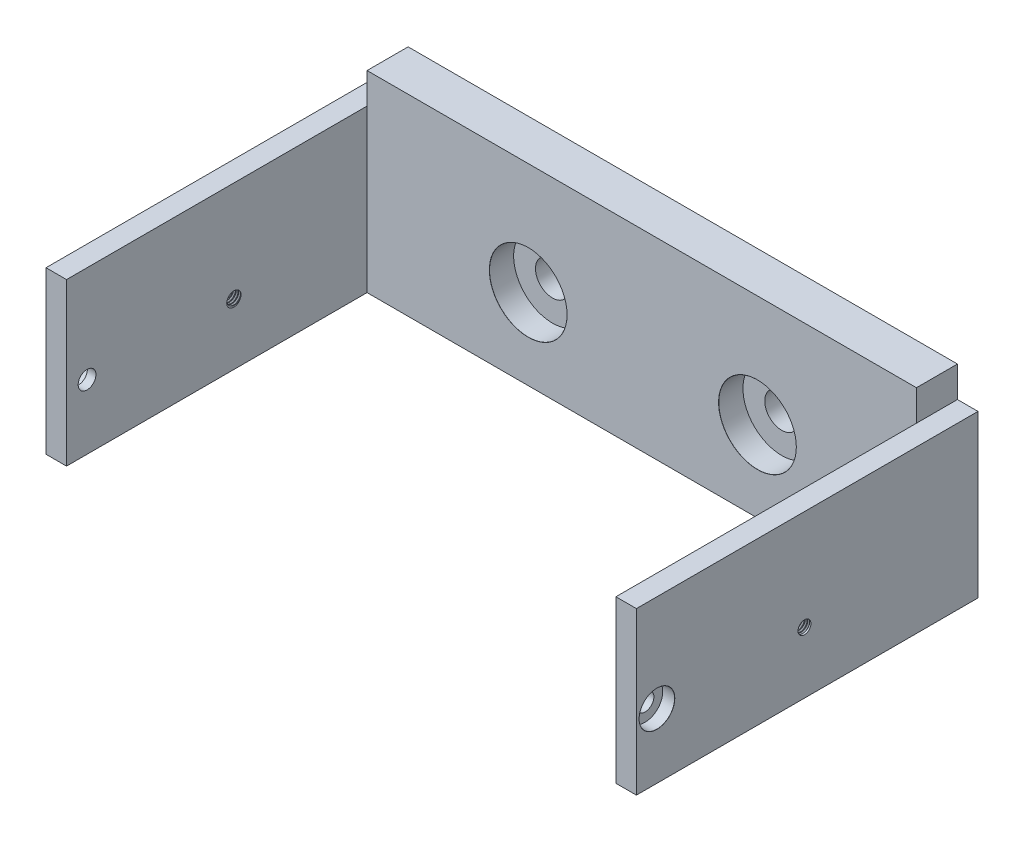
SolidWorks part; units mm, degrees
material "Liga 1060"
ref_plane "Plano frontal" through (0, 0, 0) normal (0, 0, 1) x (1, 0, 0)
ref_plane "Plano superior" through (0, 0, 0) normal (0, 1, 0) x (1, 0, 0)
ref_plane "Plano direito" through (0, 0, 0) normal (1, 0, 0) x (0, 0, -1)
sketch "Esboço1" plane through (0, 0, 0) normal (0, 0, 1) x (1, 0, 0)
  line L1 (85, -29.76) -> (-85, -29.76)
  line L2 (85, -29.76) -> (85, 29.76)
  line L3 (85, 29.76) -> (-85, 29.76)
  line L4 (-85, -29.76) -> (-85, 29.76)
  line L5 (85, -29.76) -> (-85, 29.76) construction
  line L6 (85, 29.76) -> (-85, -29.76) construction
  point P0 (0, 0)
  dimension "D1" = 170
  dimension "D2" = 59.52
extrude "Ressalto-extrusão1" add sketch "Esboço1" along normal blind 12.7
sketch "Esboço2" plane through (0, 0, 0) normal (0, 0, 1) x (1, 0, 0)
  line L0 (-85, 20.24) -> (-85, -29.76)
  line L1 (-85, 20.24) -> (-91.35, 20.24)
  line L2 (-85, -29.76) -> (-91.35, -29.76)
  line L3 (-91.35, 20.24) -> (-91.35, -29.76)
  line L4 (85, 20.24) -> (85, -29.76)
  line L5 (85, 20.24) -> (91.35, 20.24)
  line L6 (85, -29.76) -> (91.35, -29.76)
  line L7 (91.35, 20.24) -> (91.35, -29.76)
  dimension "D1" = 50
  dimension "D2" = 50
  dimension "D3" = 6.35
  dimension "D4" = 6.35
extrude "Ressalto-extrusão3" add sketch "Esboço2" along normal blind 105.7
sketch "Esboço3" plane through (91.35, 0, 0) normal (1, 0, 0) x (0, 0, -1)
  line L2 (-99.35, -29.76) -> (-99.35, 20.24) construction
  line L3 (-105.7, 20.24) -> (0, 20.24) construction
  line L4 (-105.7, -29.76) -> (0, -29.76) construction
  line L5 (-105.7, -29.76) -> (-105.7, 20.24) construction
  circle A0 centre (-99.35, -9.76) radius 2.5
  dimension "D2" = 5
  dimension "D1" = 6.35
  dimension "D3" = 20
extrude "Corte-extrusão2" cut sketch "Esboço3" against normal up to surface (6.35 mm away) up to face at (85, -4.76, 59.2)
mirror "Espelhar1" about plane through (0, 0, 0) normal (1, 0, 0) of "Corte-extrusão2"
hole_wizard "Rebaixo para parafuso com cabeça panela de M51" positions "Esboço7" profile "Esboço8" counterbore size "M5" standard "ISO" end condition through all
sketch "Esboço7" plane through (-91.35, 0, 0) normal (-1, 0, 0) x (0, 0, 1)
  point P0 (99.35, -9.76)
sketch "Esboço8" plane through (-91.35, -9.76, 99.35) normal (0, 1, 0) x (0, 0, 1)
  line L0 (0, 0) -> (0, 182.7)
  line L1 (0, 182.7) -> (2.75, 182.7)
  line L3 (2.75, 182.7) -> (2.75, 3.7)
  line L4 (5.5, 3.7) -> (2.75, 3.7)
  line L5 (5.5, 3.7) -> (5.5, 0.025)
  line L6 (5.5, 0.025) -> (5.525, 0)
  line L7 (5.525, 0) -> (0, 0)
  line L8 (-5.5, 0.025) -> (-5.525, 0) construction
  line L11 (0, -6.35) -> (0, 107.95) construction
  dimension "Thru Hole Dia." = 5.5
  dimension "Thru Hole Depth" = 182.7
  dimension "C'Bore Dia." = 11
  dimension "C'Bore Depth" = 3.7
  dimension "Near C'Sink Dia." = 11.05
  dimension "Near C'Sink Angle" = 90
hole_wizard "Furo roscado de M52" positions "Esboço9" profile "Esboço10" counterbore size "M5" standard "ISO" end condition through all
sketch "Esboço9" plane through (91.35, 0, 0) normal (1, 0, 0) x (0, 0, -1)
  point P0 (-99.35, -9.76)
sketch "Esboço10" plane through (91.35, -9.76, 99.35) normal (0, 1, 0) x (0, 0, -1)
  line L0 (0, 0) -> (0, 182.7)
  line L1 (0, 182.7) -> (2.75, 182.7)
  line L3 (2.75, 182.7) -> (2.75, 3.7)
  line L4 (5.5, 3.7) -> (2.75, 3.7)
  line L5 (5.5, 3.7) -> (5.5, 0.025)
  line L6 (5.5, 0.025) -> (5.525, 0)
  line L7 (5.525, 0) -> (0, 0)
  line L8 (-5.5, 0.025) -> (-5.525, 0) construction
  line L11 (0, -6.35) -> (0, 107.95) construction
  dimension "Thru Hole Dia." = 5.5
  dimension "Thru Hole Depth" = 182.7
  dimension "C'Bore Dia." = 11
  dimension "C'Bore Depth" = 3.7
  dimension "Near C'Sink Dia." = 11.05
  dimension "Near C'Sink Angle" = 90
sketch "Esboço11" plane through (0, 0, 12.7) normal (0, 0, 1) x (1, 0, 0)
  line L0 (-85, 20.24) -> (-85, -29.76) construction
  line L1 (-85, -4.76) -> (85, -4.76) construction
  line L2 (85, -29.76) -> (85, 20.24) construction
  circle A0 centre (-35.1326, -4.76) radius 5
  circle A1 centre (35.8074, -4.76) radius 5
  dimension "D2" = 10
  dimension "D1" = 70.94
extrude "Corte-extrusão3" cut sketch "Esboço11" against normal through all
hole_wizard "Rebaixo para parafuso com cabeça panela de M101" positions "Esboço12" profile "Esboço13" counterbore size "M10" standard "ISO"
sketch "Esboço12" plane through (0, 0, 12.7) normal (0, 0, 1) x (1, 0, 0)
  point P0 (-35.1326, -4.76)
  point P3 (35.8074, -4.76)
sketch "Esboço13" plane through (-35.1326, -4.76, 12.7) normal (1, 0, 0) x (0, -1, 0)
  line L0 (0, 0) -> (0, 23.2045)
  line L1 (0, 23.2045) -> (5.25, 20.05)
  line L2 (5.25, 20.05) -> (5.25, 7.5)
  line L3 (5.25, 7.5) -> (12, 7.5)
  line L5 (12, 7.5) -> (12, 0.025)
  line L6 (12, 0.025) -> (12.025, 0)
  line L7 (12.025, 0) -> (0, 0)
  line L8 (-12, 0.025) -> (-12.025, 0) construction
  line L10 (0, 23.2045) -> (-5.25, 20.05) construction
  line L11 (0, -6.35) -> (0, 107.95) construction
  dimension "Hole Dia." = 10.5
  dimension "Hole Depth" = 20.05
  dimension "C'Bore Dia." = 24
  dimension "C'Bore Depth" = 7.5
  dimension "Near C'Sink Dia." = 24.05
  dimension "Near C'Sink Angle" = 90
  dimension "Drill Angle" = 118
sketch "Esboço14" plane through (91.35, 0, 0) normal (1, 0, 0) x (0, 0, -1)
  line L0 (-53.7, -29.76) -> (-53.7, 20.24) construction
  line L1 (-105.7, -29.76) -> (0, -29.76) construction
  line L2 (-105.7, 20.24) -> (0, 20.24) construction
  line L3 (-105.7, -29.76) -> (-105.7, 20.24) construction
  circle A0 centre (-53.7, -10.77) radius 2
  point P10 (-53.3009, -8.77)
  point P11 (-51.2368, -8.77)
  point P12 (0, 0)
  dimension "D2" = 4
  dimension "D1" = 52
  dimension "D3" = 18.99
extrude "Corte-extrusão4" cut sketch "Esboço14" against normal through all
thread "Rosca1" pitch 0.8 method cut profile "Perfil da rosca1" start angle 0, offset 0, length 10, pitch 0.8, diameter 4
ref_plane "Plano1" through (91.35, -10.77, 55.7) normal (0, -1, 0) x (0, 0, 1)
sketch "Perfil da rosca1" plane through (91.35, -10.77, 55.7) normal (0, -1, 0) x (0, 0, 1)
  line L0 (0, 0) -> (0, 0.8) construction
  line L1 (0, 0) -> (0.433, 0.25)
  line L2 (0.433, 0.25) -> (0.433, 0.35)
  line L3 (0.433, 0.35) -> (0, 0.6)
  line L4 (0.433, 0.3) -> (0, 0.3) construction
  line L11 (0, 0) -> (0, 0.6)
  point P2 (0, 0)
  dimension "Pitch" = 0.8
  dimension "Profile_Angle" = 60
  dimension "Profile_Land" = 0.1
  dimension "Profile_Height" = 0.433
thread "Rosca2" pitch 0.8 method cut profile "Perfil da rosca2" start angle 0, offset 0, length 10, pitch 0.8, diameter 4
ref_plane "Plano2" through (-91.35, -10.77, 51.7) normal (0, -1, 0) x (0, 0, -1)
sketch "Perfil da rosca2" plane through (-91.35, -10.77, 51.7) normal (0, -1, 0) x (0, 0, -1)
  line L0 (0, 0) -> (0, 0.8) construction
  line L1 (0, 0) -> (0.433, 0.25)
  line L2 (0.433, 0.25) -> (0.433, 0.35)
  line L3 (0.433, 0.35) -> (0, 0.6)
  line L4 (0.433, 0.3) -> (0, 0.3) construction
  line L11 (0, 0) -> (0, 0.6)
  point P2 (0, 0)
  dimension "Pitch" = 0.8
  dimension "Profile_Angle" = 60
  dimension "Profile_Land" = 0.1
  dimension "Profile_Height" = 0.433
